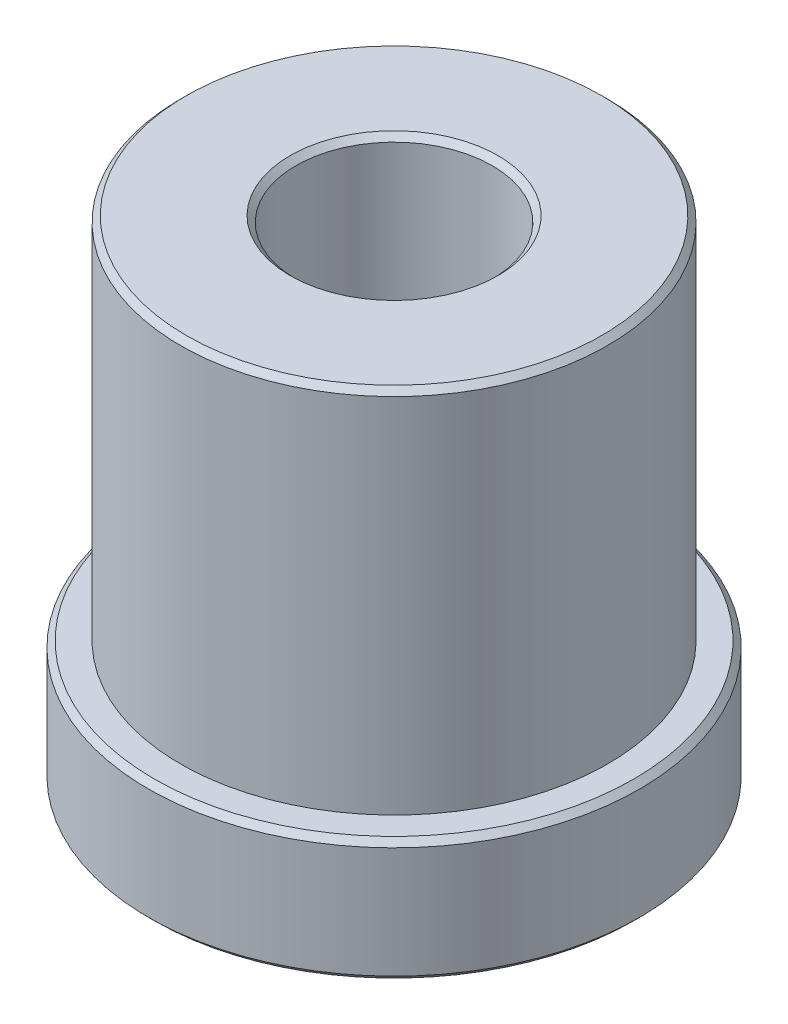
SolidWorks part; units mm, degrees
material "Nylon 101"
ref_plane "Front Plane" through (0, 0, 0) normal (0, 0, 1) x (1, 0, 0)
ref_plane "Top Plane" through (0, 0, 0) normal (0, 1, 0) x (1, 0, 0)
ref_plane "Right Plane" through (0, 0, 0) normal (1, 0, 0) x (0, 0, -1)
sketch "Sketch1" plane through (0, 0, 0) normal (0, 1, 0) x (1, 0, 0)
  circle A0 centre (0, 0) radius 11.049
  dimension "D1" = 22.098
extrude "Boss-Extrude1" add sketch "Sketch1" along normal blind 19.05
sketch "Sketch2" plane through (0, 0, 0) normal (0, -1, 0) x (1, 0, 0)
  circle A0 centre (0, 0) radius 12.7
  dimension "D1" = 25.4
extrude "Boss-Extrude2" add sketch "Sketch2" along normal blind 6.35
sketch "Sketch3" plane through (0, -6.35, 0) normal (0, -1, 0) x (1, 0, 0)
  circle A0 centre (0, 0) radius 5.08
  dimension "D1" = 10.16
extrude "Cut-Extrude1" cut sketch "Sketch3" against normal through all
sketch "Sketch4" plane through (0, -6.35, 0) normal (0, -1, 0) x (1, 0, 0)
  circle A0 centre (0, 0) radius 11.1125
  dimension "D1" = 22.225
extrude "Cut-Extrude2" cut sketch "Sketch4" against normal blind 5.5372
chamfer "Chamfer1" distance 0.3 angle 45 6 edges at (0, -0.8128, -5.08) (0, 0, -12.7) (0, -6.35, -12.7) (0, -6.35, -11.1125) (0, 19.05, 11.049) (0, 19.05, -5.08)
equation "\"D1@Chamfer1\"=.3mm"
